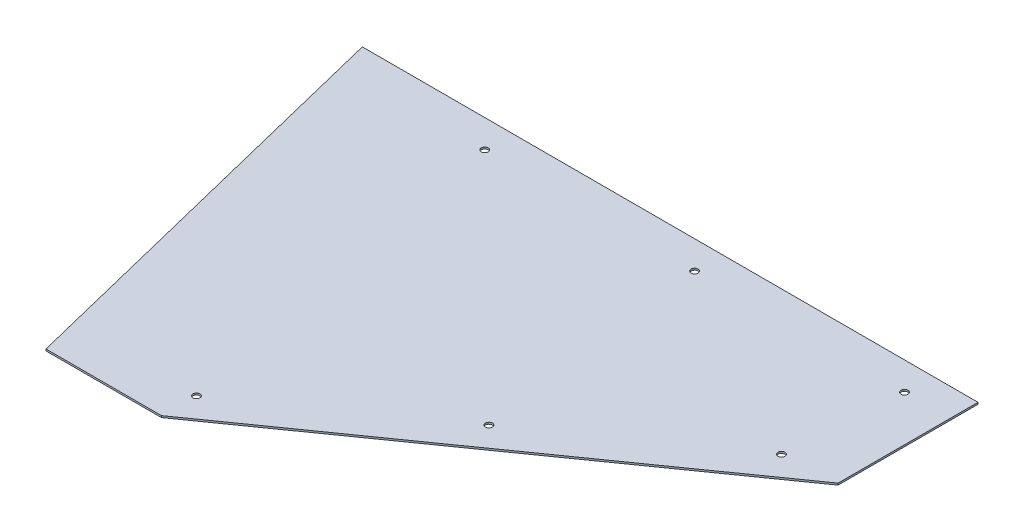
SolidWorks part; units mm, degrees
ref_plane "Front Plane" through (0, 0, 0) normal (0, 0, 1) x (1, 0, 0)
ref_plane "Top Plane" through (0, 0, 0) normal (0, 1, 0) x (1, 0, 0)
ref_plane "Right Plane" through (0, 0, 0) normal (1, 0, 0) x (0, 0, -1)
sketch "Sketch1" plane through (0, 0, 0) normal (0, 1, 0) x (1, 0, 0)
  line L0 (0, 0) -> (209.4542, 0)
  line L1 (929.8173, 762) -> (929.8173, 508)
  line L2 (929.8173, 508) -> (209.4542, 0)
  line L3 (929.8173, 762) -> (-187.7827, 762)
  line L4 (0, 0) -> (31.0108, -125.8383) construction
  line L5 (-187.7827, 762) -> (0, 0)
  line L6 (209.4542, 0) -> (31.0108, -125.8383) construction
  dimension "D1" = 914.4
  dimension "D2" = 762
  dimension "D3" = 254
  dimension "D4" = 1117.6
  dimension "D5" = 1099.82
extrude "Boss-Extrude1" add sketch "Sketch1" along normal blind 3.175
sketch "Sketch2" plane through (0, 3.175, 0) normal (0, 1, 0) x (1, 0, 0)
  line L0 (929.8173, 711.2) -> (-175.2638, 711.2) construction
  line L1 (929.8173, 508) -> (929.8173, 762) construction
  line L2 (-187.7827, 762) -> (0, 0) construction
  line L3 (929.8173, 762) -> (-187.7827, 762) construction
  line L4 (929.8173, 570.1612) -> (121.3073, 0) construction
  line L5 (0, 0) -> (209.4542, 0) construction
  line L6 (209.4542, 0) -> (929.8173, 508) construction
  line L7 (929.8173, 508) -> (900.5407, 549.5153) construction
  circle A0 centre (847.2673, 711.2) radius 6.35
  circle A1 centre (466.2673, 711.2) radius 6.35
  circle A2 centre (85.2673, 711.2) radius 6.35
  circle A3 centre (833.0783, 501.9408) radius 6.35
  circle A4 centre (521.7135, 282.3664) radius 6.35
  circle A5 centre (210.3487, 62.7919) radius 6.35
  dimension "D2" = 12.7
  dimension "D7" = 381
  dimension "D8" = 381
  dimension "D1" = 50.8
  dimension "D3" = 82.55
  dimension "D4" = 381
  dimension "D5" = 381
  dimension "D6" = 50.8
  dimension "D9" = 82.55
extrude "Cut-Extrude1" cut sketch "Sketch2" against normal up to next
